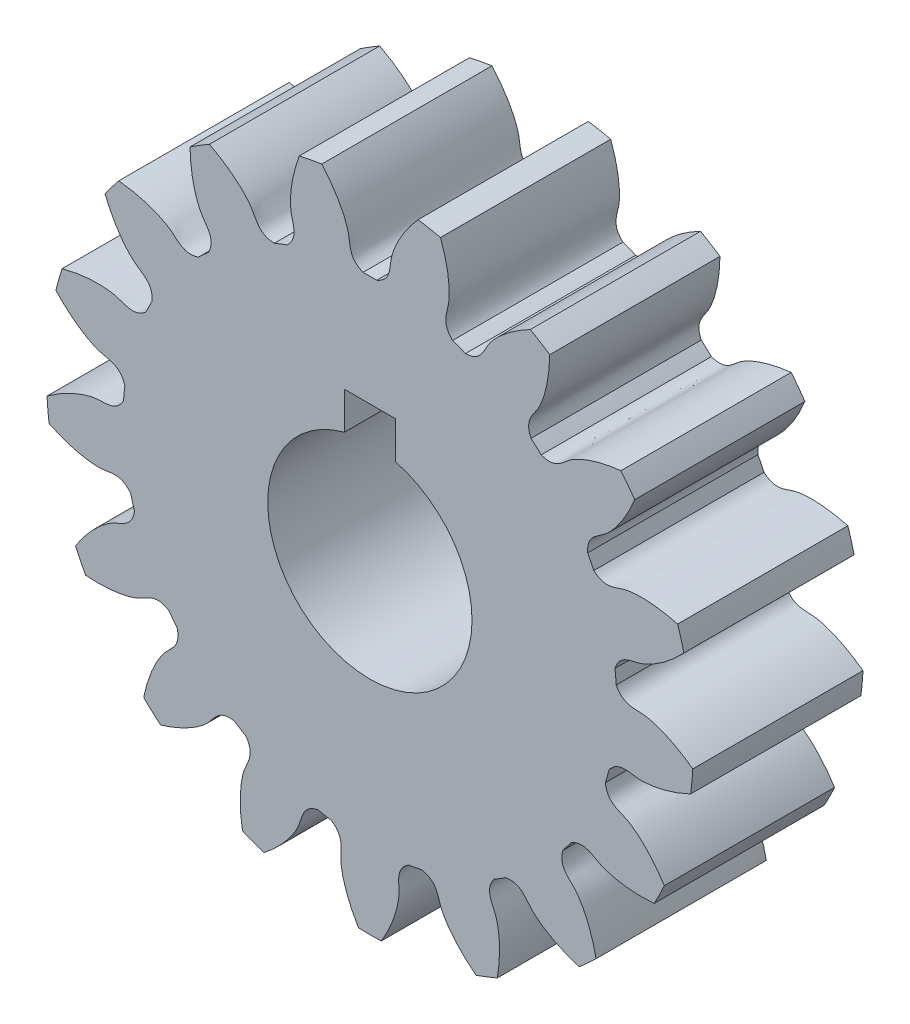
SolidWorks part; units mm, degrees
ref_plane "前视基准面" through (0, 0, 0) normal (0, 0, 1) x (1, 0, 0)
ref_plane "上视基准面" through (0, 0, 0) normal (0, 1, 0) x (1, 0, 0)
ref_plane "右视基准面" through (0, 0, 0) normal (1, 0, 0) x (0, 0, -1)
sketch "草图1" plane through (0, 0, 0) normal (0, 0, 1) x (1, 0, 0)
  circle A0 centre (0, 0) radius 19
extrude "凸台-拉伸1" add sketch "草图1" along normal blind 10
ref_axis "基准轴1" through (0, 0, -0.5) along (0, 0, 1)
sketch "草图2" plane through (0, 0, 0) normal (0, 0, 1) x (1, 0, 0)
  line L0 (0, 0) -> (0, 19) construction
  circle A0 centre (0, 0) radius 19 construction
  arc A1 (0.4034, 14.4944) -> (-0.4034, 14.4944) centre (0, 0) ccw
  arc A2 (6.2313, 21.4814) -> (-6.2313, 21.4814) centre (0, 0) ccw
  arc A3 (-6.2313, 21.4814) -> (6.2313, 21.4814) centre (0, 0) ccw construction
  spline S0 degree 3 poles (0.4034, 14.4944) (1.2558, 14.8496) (1.1324, 15.5096) (1.2766, 16.1296) (1.29, 16.1823) (1.306, 16.2408) (1.3251, 16.3052) (1.3474, 16.3752) (1.3731, 16.4508) (1.4025, 16.5319) (1.4359, 16.6184) (1.4733, 16.7101) (1.5152, 16.8068) (1.5616, 16.9086) (1.6128, 17.0151) (1.669, 17.1264) (1.7304, 17.2421) (1.7972, 17.3621) (1.8696, 17.4863) (1.9478, 17.6145) (2.032, 17.7465) (2.1224, 17.8821) (2.2191, 18.0211) (2.3223, 18.1634) (2.4322, 18.3086) (2.5489, 18.4566) (2.6727, 18.6072) (2.8035, 18.7601) (2.9417, 18.9152) (3.0873, 19.0722) (3.2404, 19.2308) (3.4012, 19.3908) (3.5698, 19.552) (3.7462, 19.7141) (3.9307, 19.8769) (4.1233, 20.0401) (4.324, 20.2035) (4.533, 20.3667) (4.7503, 20.5295) (4.9761, 20.6917) (5.2103, 20.853) (5.453, 21.0131) (5.7916, 21.2269) (6.0532, 21.3811) (6.2313, 21.4814) knots 0 0 0 0 0.193883 0.199024 0.204851 0.211363 0.21856 0.226443 0.235011 0.244265 0.254205 0.264829 0.27614 0.288136 0.300817 0.314184 0.328236 0.342973 0.358397 0.374505 0.391299 0.408779 0.426944 0.445795 0.465331 0.485552 0.506459 0.528051 0.550329 0.573293 0.596941 0.621276 0.646296 0.672001 0.698392 0.725468 0.753229 0.781677 0.810809 0.840627 0.871131 0.90232 0.934195 1 1 1 1
  spline S1 degree 3 poles (-0.4034, 14.4944) (-1.2558, 14.8496) (-1.1324, 15.5096) (-1.2766, 16.1296) (-1.29, 16.1823) (-1.306, 16.2408) (-1.3251, 16.3052) (-1.3474, 16.3752) (-1.3731, 16.4508) (-1.4025, 16.5319) (-1.4359, 16.6184) (-1.4733, 16.7101) (-1.5152, 16.8068) (-1.5616, 16.9086) (-1.6128, 17.0151) (-1.669, 17.1264) (-1.7304, 17.2421) (-1.7972, 17.3621) (-1.8696, 17.4863) (-1.9478, 17.6145) (-2.032, 17.7465) (-2.1224, 17.8821) (-2.2191, 18.0211) (-2.3223, 18.1634) (-2.4322, 18.3086) (-2.5489, 18.4566) (-2.6727, 18.6072) (-2.8035, 18.7601) (-2.9417, 18.9152) (-3.0873, 19.0722) (-3.2404, 19.2308) (-3.4012, 19.3908) (-3.5698, 19.552) (-3.7462, 19.7141) (-3.9307, 19.8769) (-4.1233, 20.0401) (-4.324, 20.2035) (-4.533, 20.3667) (-4.7503, 20.5295) (-4.9761, 20.6917) (-5.2103, 20.853) (-5.453, 21.0131) (-5.7916, 21.2269) (-6.0532, 21.3811) (-6.2313, 21.4814) knots 0 0 0 0 0.193883 0.199024 0.204851 0.211363 0.21856 0.226443 0.235011 0.244265 0.254205 0.264829 0.27614 0.288136 0.300817 0.314184 0.328236 0.342973 0.358397 0.374505 0.391299 0.408779 0.426944 0.445795 0.465331 0.485552 0.506459 0.528051 0.550329 0.573293 0.596941 0.621276 0.646296 0.672001 0.698392 0.725468 0.753229 0.781677 0.810809 0.840627 0.871131 0.90232 0.934195 1 1 1 1
extrude "切除-拉伸1" cut sketch "草图2" along normal through all
pattern_circular "阵列(圆周)1" count 17 every 21.176 about axis through (0, 0, -0.5) along (0, 0, 1) of "切除-拉伸1"
sketch "草图3" plane through (0, 0, 0) normal (0, 0, 1) x (1, 0, 0)
  circle A0 centre (0, 0) radius 17 construction
  dimension "Dn" = 34
sketch "草图4" plane through (0, 0, 10) normal (0, 0, 1) x (1, 0, 0)
  line L0 (-1.5, 4) -> (-1.5, 5.8095) construction
  line L1 (-1.5, 4) -> (1.5, 4) construction
  line L2 (-1.5, 5.8095) -> (-1.5, 8)
  line L3 (-1.5, 8) -> (1.5, 8)
  line L4 (1.5, 5.8095) -> (1.5, 8)
  line L5 (-1.5, 4) -> (1.5, 8) construction
  line L6 (-1.5, 8) -> (1.5, 4) construction
  line L7 (1.5, 4) -> (1.5, 5.8095) construction
  arc A0 (-1.5, 5.8095) -> (1.5, 5.8095) centre (0, 0) ccw
  arc A1 (0, 6) -> (-1.5, 5.8095) centre (0, 0) ccw construction
  arc A2 (1.5, 5.8095) -> (0, 6) centre (0, 0) ccw construction
  point P3 (0, 6)
  dimension "D1" = 12
  dimension "D2" = 3
  dimension "D3" = 4
extrude "切除-拉伸2" cut sketch "草图4" against normal up to next
